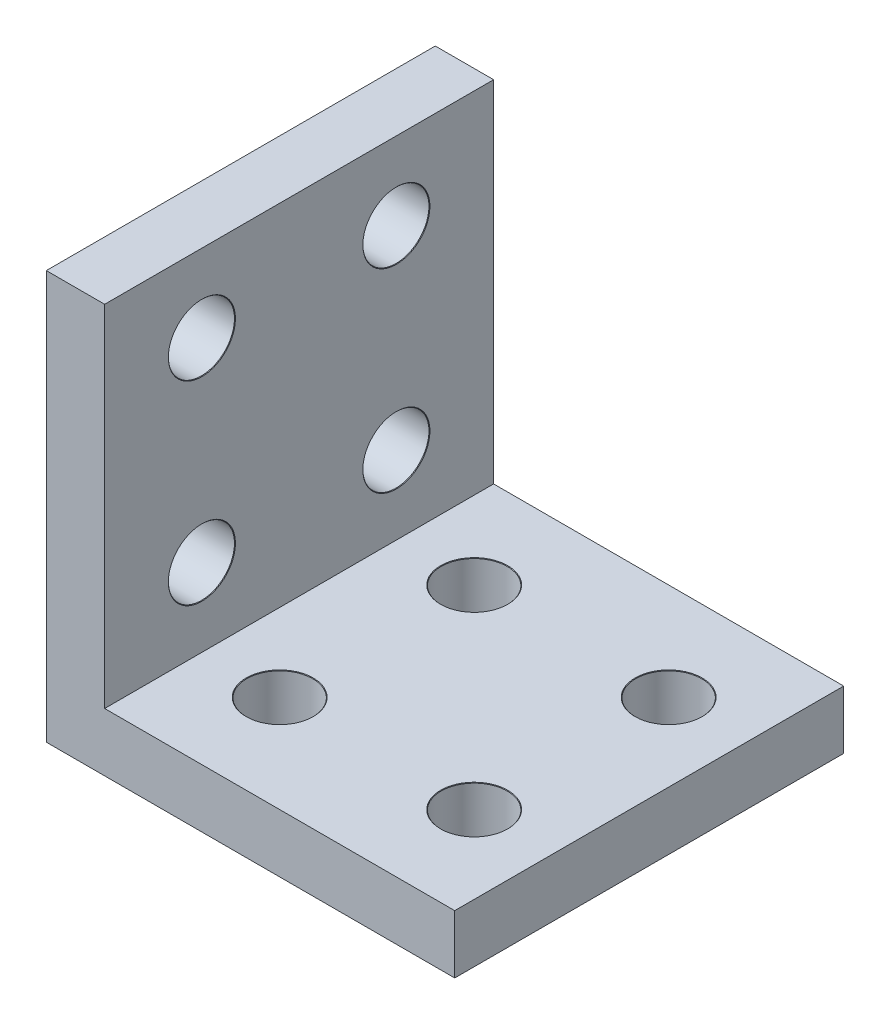
SolidWorks part; units mm, degrees
ref_plane "Front Plane" through (0, 0, 0) normal (0, 0, 1) x (1, 0, 0)
ref_plane "Top Plane" through (0, 0, 0) normal (0, 1, 0) x (1, 0, 0)
ref_plane "Right Plane" through (0, 0, 0) normal (1, 0, 0) x (0, 0, -1)
sketch "Sketch1" plane through (0, 0, 0) normal (0, 0, 1) x (1, 0, 0)
  line L0 (0, 21) -> (0, 0)
  line L1 (0, 0) -> (21, 0)
  line L2 (21, 0) -> (21, 3)
  line L3 (21, 3) -> (3, 3)
  line L4 (3, 3) -> (3, 21)
  line L5 (3, 21) -> (0, 21)
  dimension "D1" = 3
  dimension "D2" = 18
extrude "Boss-Extrude1" add sketch "Sketch1" along normal blind 20
hole_wizard "M3 Clearance Hole1" positions "Sketch2" profile "Sketch3" hole size "M3" standard "ANSI Metric" end condition through all
sketch "Sketch2" plane through (0, 3, 0) normal (0, 1, 0) x (1, 0, 0)
  line L0 (3, -10) -> (21, -10) construction
  line L1 (3, -20) -> (3, 0) construction
  line L2 (21, -20) -> (21, 0) construction
  line L4 (12, 0) -> (12, -20) construction
  line L5 (21, 0) -> (3, 0) construction
  line L6 (21, -20) -> (3, -20) construction
  line L7 (7, -15) -> (17, -15) construction
  line L8 (17, -15) -> (17, -5) construction
  line L9 (17, -5) -> (7, -5) construction
  line L10 (7, -5) -> (7, -15) construction
  point P15 (7, -5)
  point P17 (17, -5)
  point P19 (17, -15)
  point P21 (7, -15)
  point P32 (17, -10)
  point P33 (14.6505, -11.3822)
  point P34 (13.6952, -11.3822)
  point P35 (12, -5)
  point P36 (13.622, -10.622)
  dimension "D1" = 10
sketch "Sketch3" plane through (7, 3, 15) normal (1, 0, 0) x (0, 0, 1)
  line L0 (0, 0) -> (0, 3)
  line L1 (0, 3) -> (1.7, 3)
  line L2 (1.7, 3) -> (1.7, 0.025)
  line L3 (1.7, 0.025) -> (1.725, 0)
  line L5 (1.725, 0) -> (0, 0)
  line L6 (-1.7, 0.025) -> (-1.725, 0) construction
  line L11 (0, -6.35) -> (0, 107.95) construction
  dimension "Thru Hole Dia." = 3.4
  dimension "Thru Hole Depth" = 3
  dimension "Near C'Sink Dia." = 3.45
  dimension "Near C'Sink Angle" = 90
hole_wizard "M3 Clearance Hole2" positions "Sketch4" profile "Sketch5" hole size "M3" standard "ANSI Metric" end condition through all
sketch "Sketch4" plane through (3, 0, 0) normal (1, 0, 0) x (0, 0, -1)
  line L0 (-15, 7) -> (-15, 17) construction
  line L1 (-15, 17) -> (-5, 17) construction
  line L2 (-5, 17) -> (-5, 7) construction
  line L3 (-5, 7) -> (-15, 7) construction
  line L5 (-10, 3) -> (-10, 21) construction
  line L6 (-20, 21) -> (0, 21) construction
  line L8 (0, 12) -> (-20, 12) construction
  line L9 (0, 3) -> (0, 21) construction
  line L10 (-20, 3) -> (-20, 21) construction
  line L12 (-20, 3) -> (0, 3) construction
  point P0 (-15, 7)
  point P2 (-5, 7)
  point P4 (-5, 17)
  point P6 (-15, 17)
  point P30 (-10, 7)
  point P34 (-5, 12)
  dimension "D1" = 10
sketch "Sketch5" plane through (3, 7, 15) normal (0, 1, 0) x (0, 0, -1)
  line L0 (0, 0) -> (0, 3)
  line L1 (0, 3) -> (1.7, 3)
  line L2 (1.7, 3) -> (1.7, 0.025)
  line L3 (1.7, 0.025) -> (1.725, 0)
  line L5 (1.725, 0) -> (0, 0)
  line L6 (-1.7, 0.025) -> (-1.725, 0) construction
  line L11 (0, -6.35) -> (0, 107.95) construction
  dimension "Thru Hole Dia." = 3.4
  dimension "Thru Hole Depth" = 3
  dimension "Near C'Sink Dia." = 3.45
  dimension "Near C'Sink Angle" = 90
